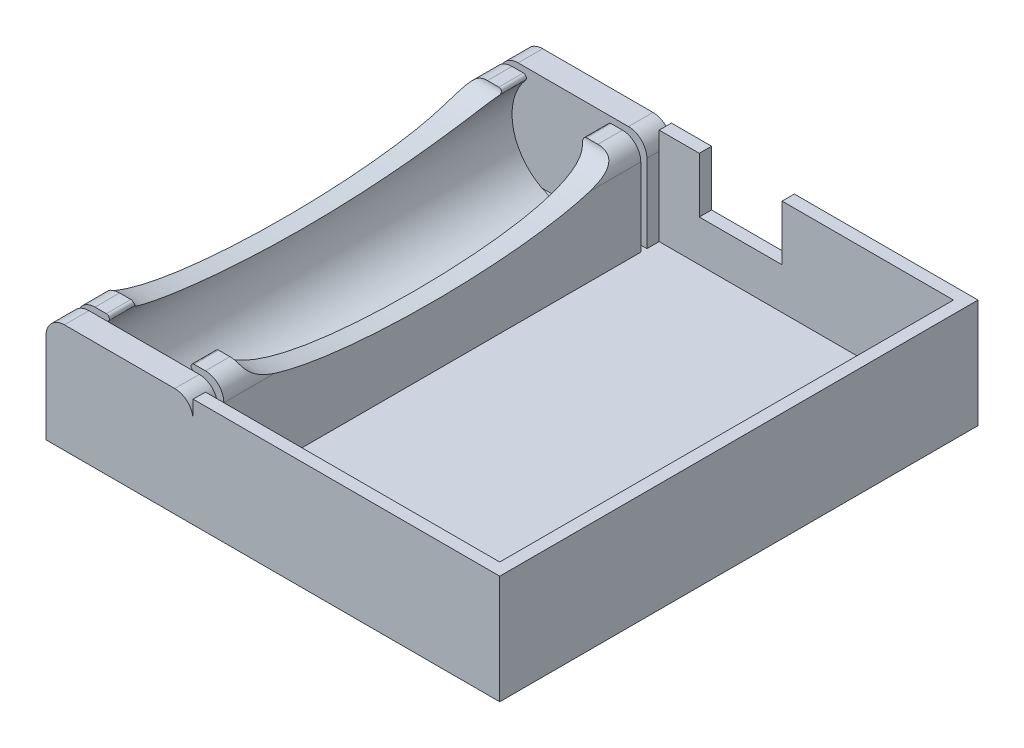
SolidWorks part; units mm, degrees
ref_plane "Alzado" through (0, 0, 0) normal (0, 0, 1) x (1, 0, 0)
ref_plane "Planta" through (0, 0, 0) normal (0, 1, 0) x (1, 0, 0)
ref_plane "Vista lateral" through (0, 0, 0) normal (1, 0, 0) x (0, 0, -1)
sketch "Croquis1" plane through (0, 0, 0) normal (0, 0, 1) x (1, 0, 0)
  line L0 (-9, 6.7459) -> (-7.1581, 6.7459)
  line L2 (-12, 3.7459) -> (-12, -11)
  line L3 (-12, -11) -> (12, -11)
  line L4 (12, 3.7459) -> (12, -11)
  line L5 (6.4708, -6.2553) -> (12, -11) construction
  line L6 (-12, -11) -> (-6.6344, -6.0815) construction
  line L7 (7.1581, 6.7459) -> (9, 6.7459)
  line L8 (12, -11) -> (-12, -11)
  line L10 (-12, -11) -> (12, -11)
  line L11 (-12, -11) -> (-12, 6.7459)
  line L12 (-12, 6.7459) -> (12, 6.7459)
  line L13 (12, -11) -> (12, 6.7459)
  arc A0 (-6.7813, 5.9172) -> (6.7813, 5.9172) centre (0, 0) ccw
  arc A1 (-9, 6.7459) -> (-12, 3.7459) centre (-9, 3.7459) ccw
  arc A2 (9, 6.7459) -> (12, 3.7459) centre (9, 3.7459) cw
  arc A3 (-6.7813, 5.9172) -> (-7.1581, 6.7459) centre (-7.1581, 6.2459) ccw
  arc A4 (7.1581, 6.7459) -> (6.7813, 5.9172) centre (7.1581, 6.2459) ccw
  point P21 (0, 0)
  dimension "D1" = 3
  dimension "D2" = 0.5
  dimension "D5" = 11
  dimension "D6" = 17.7459
  dimension "D3" = 12
  dimension "D4" = 12
extrude "Saliente-Extruir2" add sketch "Croquis1" along normal blind 70 contours A0 A4 L7 A2 L4 L3 L2 A1 L0 A3
extrude "Saliente-Extruir4" add sketch "Croquis1<6>" against normal blind 4 contours L7 A4 A0 A3 L0 A1 L2 L3 L4 A2 | A4 L12 A3 A0 region at (-8.079, 6.4475, 0) region at (0, -0.5796, 0)
sketch "Croquis1<6>" plane through (0, 0, 0) normal (0, 0, 1) x (1, 0, 0) same geometry as "Croquis1"
extrude "Saliente-Extruir5" add sketch "Croquis1<9>" along normal blind 4 from surface contours L7 A4 A0 A3 L0 A1 L2 L3 L4 A2 | A4 L12 A3 A0 region at (-8.079, 6.4475, 0) region at (0, -0.5796, 0) starting at face at (0, 1.0878, 70)
sketch "Croquis1<9>" plane through (0, 0, 0) normal (0, 0, 1) x (1, 0, 0) same geometry as "Croquis1"
sketch "Croquis5" plane through (12, 0, 0) normal (1, 0, 0) x (0, 0, -1)
  line L0 (-70, -9) -> (0, -9) construction
  line L2 (0, 5.9172) -> (0, -9)
  line L3 (0, -9) -> (-0.9995, -9)
  line L4 (-0.9995, 5.9485) -> (-0.9995, -9)
  line L5 (-74, 6.7459) -> (4, 6.7459) construction
  line L7 (-70, 5.9172) -> (-70, -9)
  line L8 (-70, -9) -> (-69.0005, -9)
  line L9 (-69.0005, 5.9485) -> (-69.0005, -9)
  line L12 (-0.9995, 5.9485) -> (-0.9995, 6.7459)
  line L13 (-0.9995, 6.7459) -> (0, 6.7459)
  line L14 (0, 5.9172) -> (0, 6.7459)
  line L16 (-70, 5.9172) -> (-70, 6.7459)
  line L17 (-70, 6.7459) -> (-69.0005, 6.7459)
  line L18 (-69.0005, 5.9485) -> (-69.0005, 6.7459)
  ellipse E0 centre (-35, 6.7459) end of major axis (-5, 6.7459) minor radius 5.8094
  dimension "D1" = 1
  dimension "D2" = 1
extrude "Cortar-Extruir1" cut sketch "Croquis5" along normal blind 15 and the other way through all
sketch "Croquis6" plane through (12, 0, 0) normal (1, 0, 0) x (0, 0, -1)
  line L0 (4, 3.7459) -> (4, -11) construction
  line L1 (-74, -11) -> (4, -11)
  line L2 (-74, -11) -> (-74, -9)
  line L3 (-72, -9) -> (2, -9)
  line L4 (4, -11) -> (4, -9)
  line L5 (4, 6.7459) -> (2, 6.7459)
  line L7 (-74, -9) -> (-74, 6.7459)
  line L9 (-72, -9) -> (-72, 6.7459)
  line L11 (4, -9) -> (4, 6.7459)
  line L13 (2, -9) -> (2, 6.7459)
  line L14 (-74, 6.7459) -> (-72, 6.7459)
  dimension "D1" = 2
extrude "Saliente-Extruir6" add sketch "Croquis6" along normal blind 50
sketch "Croquis7" plane through (0, -9, 0) normal (0, 1, 0) x (1, 0, 0)
  line L0 (62, -72) -> (12, -72) construction
  line L1 (62, 2) -> (60, 2)
  line L2 (62, 2) -> (62, -72)
  line L3 (62, -72) -> (60, -72)
  line L4 (60, 2) -> (60, -72)
  dimension "D1" = 2
extrude "Saliente-Extruir7" add sketch "Croquis7" along normal up to vertex (15.7459 mm away) up to point (62, 6.7459, 72)
sketch "Croquis9" plane through (0, -9, 0) normal (0, 1, 0) x (1, 0, 0)
  line L1 (46, -32) -> (57, -32)
  line L2 (46, -32) -> (46, -38)
  line L3 (46, -38) -> (57, -38)
  line L4 (57, -32) -> (57, -38)
  line L5 (46, -32) -> (57, -38) construction
  line L6 (46, -38) -> (57, -32) construction
  line L7 (60, 2) -> (60, -72) construction
  circle A0 centre (51.5, -53.0355) radius 2.65
  point P0 (51.5, -35)
  point P9 (60, -35)
  point P10 (57, -35)
  dimension "D1" = 11
  dimension "D2" = 6
  dimension "D3" = 5
extrude "Cortar-Extruir2" cut sketch "Croquis9" against normal blind 10
sketch "Croquis10" plane through (0, 0, -2) normal (0, 0, 1) x (1, 0, 0)
  line L0 (62, 6.7459) -> (12, 6.7459) construction
  line L1 (18.5471, 6.7459) -> (32.0471, 6.7459)
  line L2 (18.5471, 6.7459) -> (18.5471, -2.2541)
  line L3 (18.5471, -2.2541) -> (32.0471, -2.2541)
  line L4 (32.0471, 6.7459) -> (32.0471, -2.2541)
  dimension "D1" = 13.5
  dimension "D2" = 9
extrude "Cortar-Extruir3" cut sketch "Croquis10" against normal up to next
sketch "Croquis11" plane through (0, -9, 0) normal (0, 1, 0) x (1, 0, 0)
  line L3 (62, -74) -> (-12, -74)
  line L4 (62, -74) -> (62, 4)
  line L5 (62, 4) -> (-12, 4)
  line L6 (-12, -74) -> (-12, 4)
